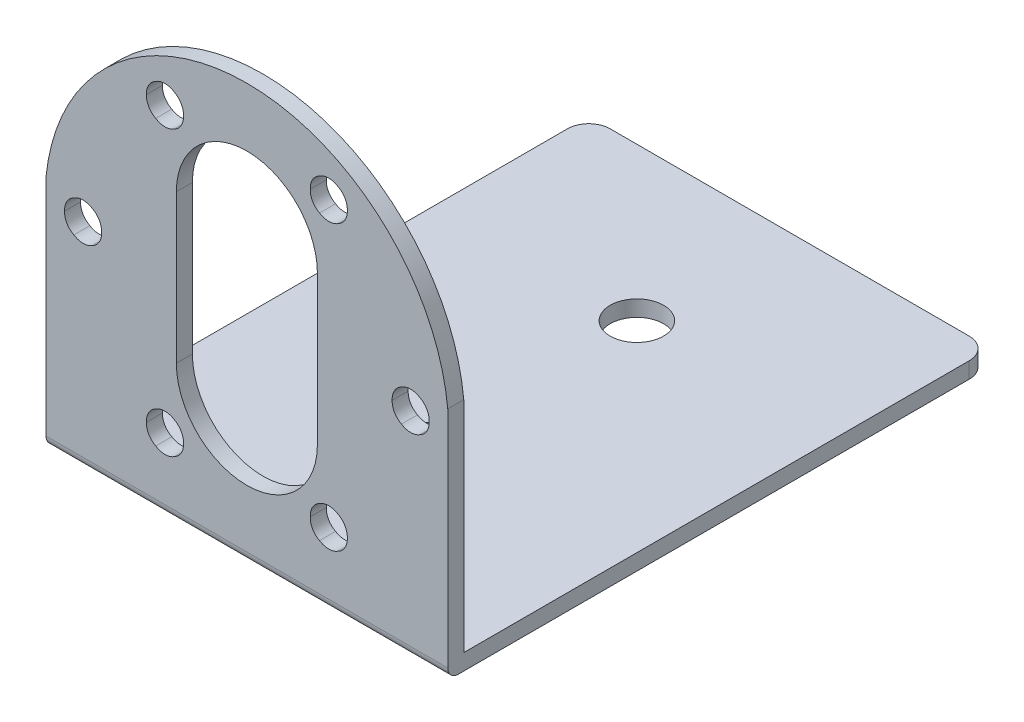
SolidWorks part; units mm, degrees
ref_plane "Front Plane" through (0, 0, 0) normal (0, 0, 1) x (1, 0, 0)
ref_plane "Top Plane" through (0, 0, 0) normal (0, 1, 0) x (1, 0, 0)
ref_plane "Right Plane" through (0, 0, 0) normal (1, 0, 0) x (0, 0, -1)
sketch "Sketch1" plane through (0, 0, 0) normal (0, 0, 1) x (1, 0, 0)
  line L0 (0, 0) -> (0, 39) construction
  line L1 (-18.8, 0) -> (18.8, 0)
  line L2 (-18.8, 0) -> (-18.8, 22)
  line L4 (18.8, 0) -> (18.8, 22)
  line L6 (-6.6, 12.9994) -> (-6.6, 26.8994)
  line L8 (6.6, 12.9994) -> (6.6, 26.8994)
  arc A0 (-18.8, 22) -> (18.8, 22) centre (0, 20.1047) cw
  arc A1 (-6.6, 26.8994) -> (6.6, 26.8994) centre (0, 26.9) cw
  arc A2 (-6.6, 12.9994) -> (6.6, 12.9994) centre (0, 13) ccw
  dimension "D3" = 39
  dimension "D5" = 27.1
  dimension "D6" = 5.5
  dimension "D1" = 37.6
  dimension "D2" = 22
  dimension "D4" = 13.2
  dimension "D7" = 13.9
extrude "Boss-Extrude1" add sketch "Sketch1" along normal blind 1.5
sketch "Sketch2" plane through (0, 0, 0) normal (0, -1, 0) x (1, 0, 0)
  line L0 (18.8, 1.5) -> (18.8, 0) construction
  line L1 (-18.8, 1.5) -> (18.8, 1.5)
  line L2 (-18.8, 1.5) -> (-18.8, -49.3)
  line L3 (-18.8, -49.3) -> (18.8, -49.3)
  line L4 (18.8, 1.5) -> (18.8, -49.3)
  dimension "D1" = 50.8
extrude "Boss-Extrude2" add sketch "Sketch2" against normal blind 1.5
fillet "Fillet1" radius 1 1 edges at (0, 0, 1.5)
fillet "Fillet2" radius 2 2 edges at (-18.8, 0.75, -49.3) (18.8, 0.75, -49.3)
sketch "Sketch3" plane through (0, 0, 0) normal (0, -1, 0) x (1, 0, 0)
  line L0 (-16.8, -49.3) -> (16.8, -49.3) construction
  line L1 (-18.8, 0.5) -> (-18.8, -47.3) construction
  circle A0 centre (-15.6, -44.5) radius 1.6
  dimension "D1" = 3.2
  dimension "D2" = 4.8
  dimension "D3" = 3.2
sketch "Sketch4" plane through (0, 0, 1.5) normal (0, 0, 1) x (1, 0, 0)
  line L0 (0, 0) -> (0, 39) construction
  line L1 (-7.6648, 33.2258) -> (-5.815, 30.0218) construction
  line L2 (-5.815, 30.0218) -> (0, 19.95) construction
  line L3 (0, 19.95) -> (-5.815, 9.8782) construction
  line L4 (0, 19.95) -> (5.815, 9.8782) construction
  line L5 (5.815, 9.8782) -> (7.6648, 6.6742) construction
  line L6 (0, 19.95) -> (5.815, 30.0218) construction
  line L7 (5.815, 30.0218) -> (7.6648, 33.2258) construction
  line L8 (-5.815, 9.8782) -> (-7.6648, 6.6742) construction
  line L9 (7.325, 33.2258) -> (7.6648, 33.2258) construction
  line L10 (7.6648, 33.2258) -> (9.5146, 36.4297) construction
  circle A0 centre (7.6648, 33.2258) radius 1.6
  arc A1 (18.8, 22) -> (-18.8, 22) centre (0, 20.1047) ccw construction
  circle A3 centre (15.3295, 19.95) radius 1.6
  circle A4 centre (7.6648, 6.6742) radius 1.6
  circle A5 centre (-7.6648, 6.6742) radius 1.6
  circle A6 centre (-15.3295, 19.95) radius 1.6
  circle A7 centre (-7.6648, 33.2258) radius 1.6
  arc A8 (-6.6, 12.9994) -> (6.6, 12.9994) centre (0, 13) ccw construction
  arc A9 (6.6, 26.8994) -> (-6.6, 26.8994) centre (0, 26.9) ccw construction
  point P26 (0, 19.95)
  dimension "D1" = 3.2
  dimension "D2" = 6
extrude "Cut-Extrude2" cut sketch "Sketch4" against normal up to next
pattern_circular "CirPattern1" count 6 over 360 about axis through (0, 20.1047, 1.5) along (0, 0, -1) of "Cut-Extrude2"
sketch "Szkic1" plane through (0, 1.5, 0) normal (0, 1, 0) x (1, 0, 0)
  line L0 (18.8, 0) -> (-18.8, 0) construction
  circle A0 centre (0, 15) radius 2.5
  circle A1 centre (0, 35) radius 2.5
  dimension "D1" = 5
  dimension "D2" = 5
  dimension "D3" = 20
  dimension "D4" = 15
extrude "Wytnij-wyciągnięcie1" cut sketch "Szkic1" against normal blind 10
sketch "Szkic2" plane through (0, 1.5, 0) normal (0, 1, 0) x (1, 0, 0)
  line L0 (-16.8, 49.3) -> (16.8, 49.3) construction
  line L1 (18.8, 0) -> (18.8, 49.3)
  line L2 (18.8, 49.3) -> (-18.8, 49.3)
  line L3 (-18.8, 0) -> (-18.8, 49.3)
  ellipse E0 centre (0, -45.5597) end of major axis (0, -140.4194) minor radius 21.434 (18.8, 0) -> (-18.8, 0) ccw
